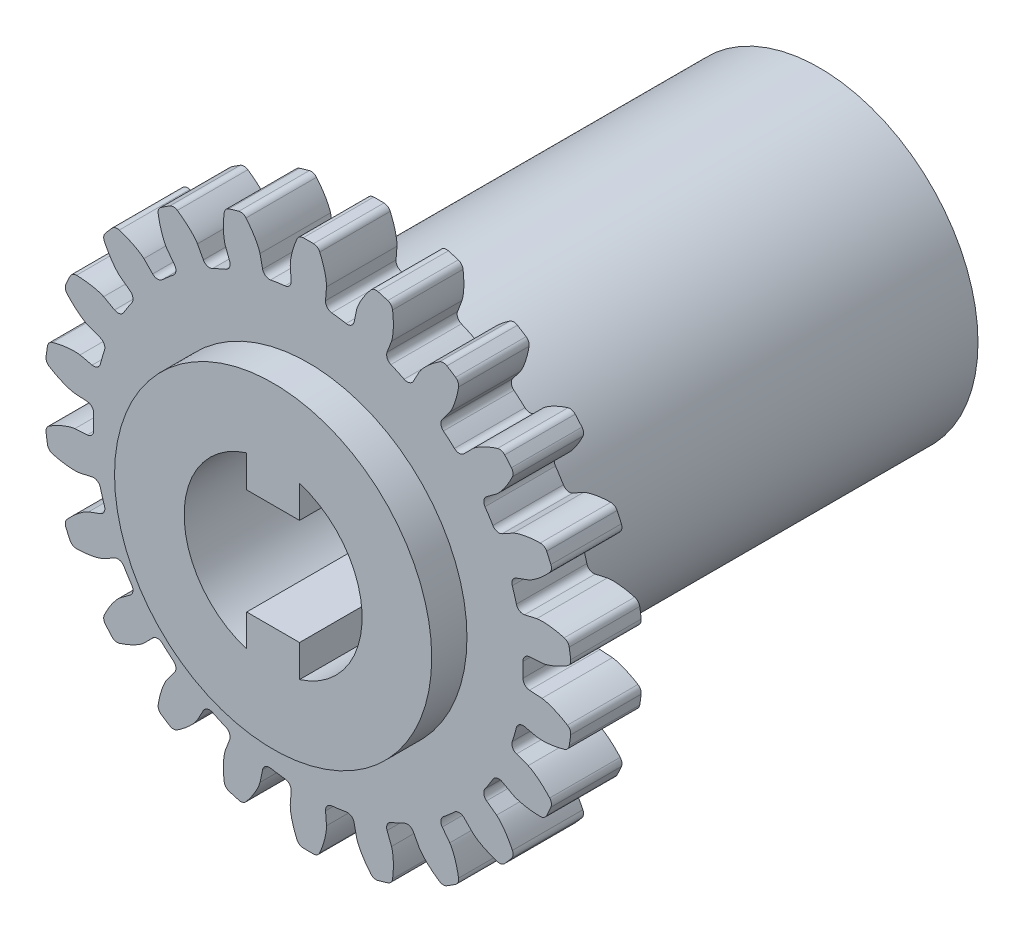
SolidWorks part; units mm, degrees
material "Brass"
ref_plane "Front Plane" through (0, 0, 0) normal (0, 0, 1) x (1, 0, 0)
ref_plane "Top Plane" through (0, 0, 0) normal (0, 1, 0) x (1, 0, 0)
ref_plane "Right Plane" through (0, 0, 0) normal (1, 0, 0) x (0, 0, -1)
sketch "Sketch1" plane through (0, 0, 0) normal (0, 0, 1) x (1, 0, 0)
  circle A0 centre (0, 0) radius 15
  dimension "D1" = 30
extrude "Boss-Extrude1" add sketch "Sketch1" along normal blind 4
sketch "Sketch2" plane through (0, 0, 4) normal (0, 0, 1) x (1, 0, 0)
  line L0 (13.2532, 0.866) -> (0, 0) construction
  line L1 (0, 0) -> (13.2532, -0.866) construction
  line L2 (12.1616, 0.7947) -> (13.2532, 0.866)
  line L3 (12.1616, -0.7947) -> (13.2532, -0.866)
  circle A0 centre (0, 0) radius 15 construction
  circle A1 centre (0, 0) radius 13.2815 construction
  circle A2 centre (0, 0) radius 13.75 construction
  circle A3 centre (0, 0) radius 12.1875 construction
  arc A4 (14.9146, 1.5987) -> (14.9146, -1.5987) centre (3.6281, 0) cw
  arc A5 (12.1616, -0.7947) -> (12.1616, 0.7947) centre (0, 0) ccw
  spline S0 degree 4 poles (13.2532, 0.866) (13.2559, 0.8662) (13.2635, 0.8669) (13.2777, 0.8685) (13.301, 0.8717) (13.3305, 0.8765) (13.3686, 0.8837) (13.4134, 0.8932) (13.4625, 0.9048) (13.5157, 0.9187) (13.5687, 0.9338) (13.6214, 0.9498) (13.6738, 0.9667) (13.7371, 0.9884) (13.8128, 1.0158) (13.9009, 1.0502) (14.0004, 1.0918) (14.1013, 1.1371) (14.2002, 1.1839) (14.2997, 1.2339) (14.3956, 1.2842) (14.4946, 1.3392) (14.5858, 1.3913) (14.6873, 1.4527) (14.7691, 1.5032) (14.8762, 1.5729) (14.9393, 1.6151) (15.0129, 1.6655) (15.0454, 1.6885) (15.0655, 1.7026) knots 0 0 0 0 0 0.005377 0.015084 0.028532 0.04661 0.064855 0.092111 0.119476 0.146842 0.174209 0.201575 0.228941 0.256307 0.307035 0.361767 0.4165 0.471232 0.525964 0.580697 0.635429 0.690161 0.744894 0.799626 0.854358 0.909091 0.954545 1 1 1 1 1 construction
  spline S1 degree 4 poles (13.2532, 0.866) (13.2559, 0.8662) (13.2635, 0.8669) (13.2777, 0.8685) (13.301, 0.8717) (13.3305, 0.8765) (13.3686, 0.8837) (13.4134, 0.8932) (13.4625, 0.9048) (13.5157, 0.9187) (13.5687, 0.9338) (13.6214, 0.9498) (13.6738, 0.9667) (13.7371, 0.9884) (13.8128, 1.0158) (13.9009, 1.0502) (14.0004, 1.0918) (14.1013, 1.1371) (14.2002, 1.1839) (14.2997, 1.2339) (14.3956, 1.2842) (14.4946, 1.3392) (14.5858, 1.3913) (14.6873, 1.4527) (14.7691, 1.5032) (14.853, 1.5578) (14.8938, 1.5848) (14.9146, 1.5987) knots 0 0 0 0 0 0.005377 0.015084 0.028532 0.04661 0.064855 0.092111 0.119476 0.146842 0.174209 0.201575 0.228941 0.256307 0.307035 0.361767 0.4165 0.471232 0.525964 0.580697 0.635429 0.690161 0.744894 0.799626 0.854358 0.909091 0.909091 0.909091 0.909091 0.909091
  spline S2 degree 4 poles (13.2532, -0.866) (13.2559, -0.8662) (13.2635, -0.8669) (13.2777, -0.8685) (13.301, -0.8717) (13.3305, -0.8765) (13.3686, -0.8837) (13.4134, -0.8932) (13.4625, -0.9048) (13.5157, -0.9187) (13.5687, -0.9338) (13.6214, -0.9498) (13.6738, -0.9667) (13.7371, -0.9884) (13.8128, -1.0158) (13.9009, -1.0502) (14.0004, -1.0918) (14.1013, -1.1371) (14.2002, -1.1839) (14.2997, -1.2339) (14.3956, -1.2842) (14.4946, -1.3392) (14.5858, -1.3913) (14.6873, -1.4527) (14.7691, -1.5032) (14.8762, -1.5729) (14.9393, -1.6151) (15.0129, -1.6655) (15.0454, -1.6885) (15.0655, -1.7026) knots 0 0 0 0 0 0.005377 0.015084 0.028532 0.04661 0.064855 0.092111 0.119476 0.146842 0.174209 0.201575 0.228941 0.256307 0.307035 0.361767 0.4165 0.471232 0.525964 0.580697 0.635429 0.690161 0.744894 0.799626 0.854358 0.909091 0.954545 1 1 1 1 1 construction
  spline S3 degree 4 poles (13.2532, -0.866) (13.2559, -0.8662) (13.2635, -0.8669) (13.2777, -0.8685) (13.301, -0.8717) (13.3305, -0.8765) (13.3686, -0.8837) (13.4134, -0.8932) (13.4625, -0.9048) (13.5157, -0.9187) (13.5687, -0.9338) (13.6214, -0.9498) (13.6738, -0.9667) (13.7371, -0.9884) (13.8128, -1.0158) (13.9009, -1.0502) (14.0004, -1.0918) (14.1013, -1.1371) (14.2002, -1.1839) (14.2997, -1.2339) (14.3956, -1.2842) (14.4946, -1.3392) (14.5858, -1.3913) (14.6873, -1.4527) (14.7691, -1.5032) (14.853, -1.5578) (14.8938, -1.5848) (14.9146, -1.5987) knots 0 0 0 0 0 0.005377 0.015084 0.028532 0.04661 0.064855 0.092111 0.119476 0.146842 0.174209 0.201575 0.228941 0.256307 0.307035 0.361767 0.4165 0.471232 0.525964 0.580697 0.635429 0.690161 0.744894 0.799626 0.854358 0.909091 0.909091 0.909091 0.909091 0.909091
  circle M4 centre (0, 0) radius 15
  dimension "D1" = 30
  dimension "D2" = 24.375
  dimension "D3" = 27.5
  dimension "D4" = 26.563
extrude "Cut-Extrude1" cut sketch "Sketch2" against normal through all contours L3 S3 S1 L2 A5 M4 region at (13.7532, 0, 4)
sketch "Mate" plane through (0, 0, 0) normal (0, 0, 1) x (1, 0, 0)
  circle A0 centre (0, 0) radius 13.75
  circle A1 centre (0, 0) radius 13.75 construction
fillet "Fillet1" radius 0.3934 4 edges at (12.1616, -0.7947, 2) (12.1616, 0.7947, 2) (14.9146, -1.5987, 2) (14.9146, 1.5987, 2)
pattern_circular "CirPattern1" count 22 over 360 about axis through (0, 0, 0) along (0, 0, 1) of "Cut-Extrude1", "Fillet1"
sketch "Sketch4" plane through (0, 0, 0) normal (0, 0, 1) x (1, 0, 0)
  circle A0 centre (0, 0) radius 9
  dimension "D1" = 18
extrude "Boss-Extrude2" add sketch "Sketch4" against normal blind 25 and the other way blind 6
sketch "Sketch3" plane through (0, 0, 0) normal (0, 0, 1) x (1, 0, 0)
  line L0 (-1.5, 4.8221) -> (-1.5, 3)
  line L1 (-1.5, 3) -> (1.5, 3)
  line L2 (1.5, 3) -> (1.5, 4.8221)
  line L3 (1.5, -4.8221) -> (1.5, -3)
  line L4 (1.5, -3) -> (-1.5, -3)
  line L5 (-1.5, -3) -> (-1.5, -4.8221)
  circle A0 centre (0, 0) radius 5.05
  dimension "D1" = 10.1
  dimension "D2" = 3
  dimension "D3" = 6
extrude "Cut-Extrude2" cut sketch "Sketch3" along normal through all both and the other way through all contours L0 A0 L5 L4 L3 L2 L1 region at (0, 0, 0)
equation "\"DiametralPitch\"= 0.8"
equation "\"NumTeeth\"= 22"
equation "\"Addendum\"= 1 / \"DiametralPitch\""
equation "\"Dedendum\"= 1.25 / \"DiametralPitch\""
equation "\"WorkingDepth\"= 2 / \"DiametralPitch\""
equation "\"WholeDepth\"= 2.25 / \"DiametralPitch\""
equation "\"Clearance\"= 0.25 / \"DiametralPitch\""
equation "\"ToothThickness\"= 1.5708 / \"DiametralPitch\""
equation "\"CircularPitch\"= pi / \"DiametralPitch\""
equation "\"PitchCircle\"= \"NumTeeth\" / \"DiametralPitch\""
equation "\"OutsideDiameter\"= ( \"NumTeeth\" + 2 ) / \"DiametralPitch\""
equation "\"AddendumCircle\"= \"PitchCircle\" + ( 2 * \"Addendum\" )"
equation "\"DedendumCircle\"= \"PitchCircle\" - ( 2 * \"Dedendum\" )"
equation "\"PitchAngle\"= 360deg / \"NumTeeth\""
equation "\"PressureAngle\"= 15deg"
equation "\"Width\"= 4mm"
equation "\"Fillet\"= \"Clearance\" * cos ( \"PressureAngle\" ) * tan ( ( 90 + \"PressureAngle\" ) / 2 )"
equation "\"BaseCircle\"= \"PitchCircle\" * cos ( \"PressureAngle\" )"
equation "\"Alpha\"= sqr ( \"PitchCircle\" ^ 2 - \"BaseCircle\" ^ 2 ) / \"BaseCircle\" * 180 / PI - \"PressureAngle\""
equation "\"Beta\"= ( \"PitchAngle\" / 4 - \"Alpha\" )"
equation "\"Phi\"= sqr ( ( \"AddendumCircle\" / 2 ) ^ 2 - ( \"BaseCircle\" / 2 ) ^ 2 ) / ( \"BaseCircle\" / 2 )"
equation "\"D1@Sketch1\"=\"OutsideDiameter\""
equation "\"D1@Boss-Extrude1\"=\"Width\""
equation "\"D1@Sketch2\"=\"OutsideDiameter\""
equation "\"D2@Sketch2\"=\"DedendumCircle\""
equation "\"D3@Sketch2\"=\"PitchCircle\""
equation "\"D4@Sketch2\"=\"BaseCircle\""
equation "\"D1@Fillet1\"=\"Fillet\""
equation "\"D1@CirPattern1\"=\"NumTeeth\""
